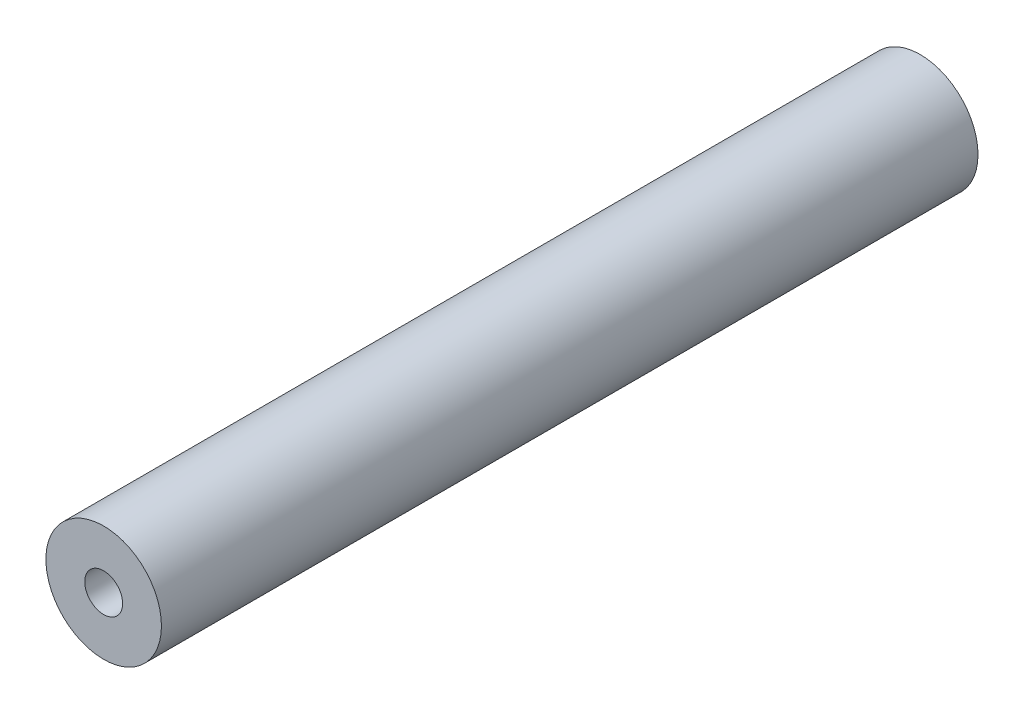
SolidWorks part; units mm, degrees
ref_plane "Front Plane" through (0, 0, 0) normal (0, 0, 1) x (1, 0, 0)
ref_plane "Top Plane" through (0, 0, 0) normal (0, 1, 0) x (1, 0, 0)
ref_plane "Right Plane" through (0, 0, 0) normal (1, 0, 0) x (0, 0, -1)
sketch "Sketch1" plane through (0, 0, 0) normal (0, 0, 1) x (1, 0, 0)
  circle A0 centre (0, 0) radius 7.5
  dimension "D1" = 15
extrude "Boss-Extrude1" add sketch "Sketch1" along normal mid plane 106
sketch "Sketch2" plane through (0, 0, 53) normal (0, 0, 1) x (1, 0, 0)
  circle A0 centre (0, 0) radius 2.46
  dimension "D1" = 4.92
extrude "Cut-Extrude1" cut sketch "Sketch2" against normal blind 15
mirror "Mirror1" about plane through (0, 0, 0) normal (0, 0, 1) of "Cut-Extrude1"
